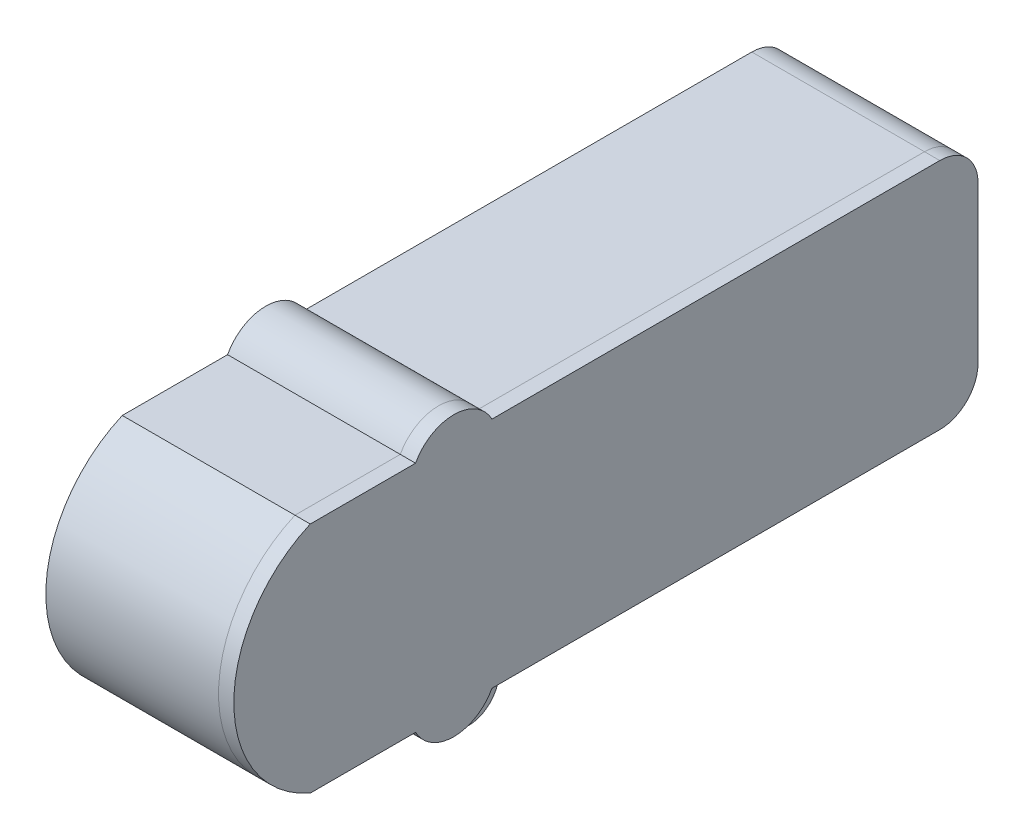
SolidWorks part; units mm, degrees
ref_plane "Front Plane" through (0, 0, 0) normal (0, 0, 1) x (1, 0, 0)
ref_plane "Top Plane" through (0, 0, 0) normal (0, 1, 0) x (1, 0, 0)
ref_plane "Right Plane" through (0, 0, 0) normal (1, 0, 0) x (0, 0, -1)
sketch "Sketch1" plane through (0, 0, 0) normal (1, 0, 0) x (0, 0, -1)
  line L0 (-25.32, -11.25) -> (8.38, -11.25) construction
  line L1 (20.38, -15.25) -> (-67, -15.25)
  line L2 (20.38, -15.25) -> (20.38, 15.25)
  line L3 (20.38, 15.25) -> (-67, 15.25)
  line L4 (-67, -15.25) -> (-67, 15.25) construction
  line L5 (11.38, -8.25) -> (11.38, 8.25) construction
  line L6 (-25.32, -11.25) -> (8.38, -11.25) construction
  line L7 (11.38, -8.25) -> (11.38, 8.25) construction
  line L8 (8.38, 11.25) -> (-25.32, 11.25) construction
  line L9 (8.38, 11.25) -> (-25.32, 11.25) construction
  line L10 (8.38, 15.25) -> (8.38, 11.25) construction
  line L11 (20.38, 8.25) -> (11.38, 8.25) construction
  line L12 (8.38, -11.25) -> (8.38, -15.25) construction
  line L13 (16.38, 2) -> (16.38, -2) construction
  line L14 (16.38, 2) -> (16.38, -2) construction
  line L15 (16.38, 2) -> (20.38, 2) construction
  line L17 (-67, 0) -> (-77, 0) construction
  arc A0 (-67, 15.25) -> (-67, -15.25) centre (-60.3719, 0) ccw
  dimension "D2" = 10
  dimension "D1" = 4
extrude "Boss-Extrude1" add sketch "Sketch1" against normal blind 3
fillet "Fillet1" radius 5 2 edges at (-1.5, -15.25, -20.38) (-1.5, 15.25, -20.38)
sketch "Sketch2" plane through (0, 0, 0) normal (1, 0, 0) x (0, 0, -1)
  line L0 (-66.3438, -12.25) -> (15.38, -12.25)
  line L1 (17.38, -10.25) -> (17.38, 10.25)
  line L2 (15.38, 12.25) -> (-66.3438, 12.25)
  line L3 (-67, -15.25) -> (15.38, -15.25)
  line L4 (20.38, -10.25) -> (20.38, 10.25)
  line L5 (15.38, 15.25) -> (-67, 15.25)
  line L6 (-67, -15.25) -> (15.38, -15.25)
  line L7 (20.38, -10.25) -> (20.38, 10.25)
  line L8 (15.38, 15.25) -> (-67, 15.25)
  arc A0 (15.38, -12.25) -> (17.38, -10.25) centre (15.38, -10.25) ccw
  arc A1 (17.38, 10.25) -> (15.38, 12.25) centre (15.38, 10.25) ccw
  arc A2 (-66.3438, 12.25) -> (-66.3438, -12.25) centre (-60.3719, 0) ccw
  arc A3 (15.38, -15.25) -> (20.38, -10.25) centre (15.38, -10.25) ccw
  arc A4 (20.38, 10.25) -> (15.38, 15.25) centre (15.38, 10.25) ccw
  arc A5 (-67, 15.25) -> (-67, -15.25) centre (-60.3719, 0) ccw
  arc A6 (15.38, -15.25) -> (20.38, -10.25) centre (15.38, -10.25) ccw
  arc A7 (20.38, 10.25) -> (15.38, 15.25) centre (15.38, 10.25) ccw
  arc A8 (-67, 15.25) -> (-67, -15.25) centre (-60.3719, 0) ccw
  dimension "D1" = 0
  dimension "D2" = 3
extrude "Boss-Extrude2" add sketch "Sketch2" along normal offset from surface (19.6 mm away) 1 offset beyond the face yes
sketch "Sketch3" plane through (0, 0, 0) normal (1, 0, 0) x (0, 0, -1)
  line L0 (-34.62, 12.25) -> (-34.62, 11.25)
  line L1 (-66.3438, 12.25) -> (15.38, 12.25) construction
  line L2 (-34.62, 11.25) -> (10.38, 11.25)
  line L3 (11.38, 10.25) -> (11.38, -12.25)
  line L4 (15.38, -12.25) -> (-66.3438, -12.25) construction
  line L5 (11.38, -12.25) -> (15.38, -12.25)
  line L6 (11.38, 8.25) -> (11.38, -8.25) construction
  line L7 (-25.32, 11.25) -> (8.38, 11.25) construction
  line L8 (15.38, 12.25) -> (-66.3438, 12.25) construction
  line L9 (17.38, -10.25) -> (17.38, 10.25) construction
  line L10 (15.38, 12.25) -> (-34.62, 12.25)
  line L11 (17.38, -10.25) -> (17.38, 10.25)
  arc A0 (10.38, 11.25) -> (11.38, 10.25) centre (10.38, 10.25) cw
  arc A1 (17.38, 10.25) -> (15.38, 12.25) centre (15.38, 10.25) ccw construction
  arc A2 (15.38, -12.25) -> (17.38, -10.25) centre (15.38, -10.25) ccw construction
  arc A3 (17.38, 10.25) -> (15.38, 12.25) centre (15.38, 10.25) ccw
  arc A4 (15.38, -12.25) -> (17.38, -10.25) centre (15.38, -10.25) ccw
  dimension "D1" = 1
  dimension "D2" = 45
extrude "Boss-Extrude5" add sketch "Sketch3" along normal up to surface (18.6 mm away)
sketch "Sketch5" plane through (18.6, 0, 0) normal (1, 0, 0) x (0, 0, -1)
  line L4 (17.38, 10.25) -> (17.38, -10.25) construction
  line L5 (10.38, -3.5) -> (17.38, -3.5)
  line L6 (10.38, -3.5) -> (10.38, 3.5)
  line L7 (10.38, 3.5) -> (17.38, 3.5)
  line L12 (17.38, -3.5) -> (17.38, 3.5)
  line L13 (10.38, -3.5) -> (17.38, 3.5) construction
  line L14 (10.38, 3.5) -> (17.38, -3.5) construction
  arc A2 (15.18, 0) -> (12.58, 0) centre (13.88, 0) ccw construction
  arc A3 (15.18, 0) -> (12.58, 0) centre (13.88, 0) ccw construction
extrude "Cut-Extrude1" cut sketch "Sketch5" against normal offset from surface (11.8 mm away) 1 offset beyond the face yes
sketch "Sketch6" plane through (0, 0, 0) normal (1, 0, 0) x (0, 0, -1)
  line L0 (-49.019, 14.805) -> (-47.419, 14.805) construction
  line L1 (-49.019, 14.805) -> (-47.419, 14.805) construction
  line L2 (-49.019, -15.055) -> (-47.419, -15.055) construction
  line L3 (-49.019, -15.055) -> (-47.419, -15.055) construction
  line L4 (-49.019, 14.805) -> (-49.019, -15.055) construction
  line L5 (-47.419, -15.055) -> (-47.419, 14.805) construction
  line L6 (-50.019, 15.805) -> (-46.419, 15.805)
  line L7 (-46.419, -16.055) -> (-46.419, 15.805)
  line L8 (-50.019, -16.055) -> (-46.419, -16.055)
  line L9 (-50.019, 15.805) -> (-50.019, -16.055)
  dimension "D1" = 1
extrude "Cut-Extrude2" cut sketch "Sketch6" along normal through all
sketch "Sketch7" plane through (-3, 0, 0) normal (-1, 0, 0) x (0, 0, 1)
  line L0 (67, 15.25) -> (50.019, 15.25) construction
  line L1 (46.419, 15.25) -> (-15.38, 15.25) construction
  line L6 (48.219, 15.25) -> (48.219, 18.25) construction
  line L7 (50.019, 15.25) -> (46.419, 15.25) construction
  line L8 (53.219, 15.25) -> (43.219, 15.25)
  line L9 (0, 0) -> (12.8243, 0) construction
  line L10 (48.219, -15.25) -> (48.219, -18.25) construction
  line L11 (53.219, -15.25) -> (43.219, -15.25)
  arc A0 (53.219, 15.25) -> (43.219, 15.25) centre (48.219, 12.5833) ccw
  arc A1 (53.219, -15.25) -> (43.219, -15.25) centre (48.219, -12.5833) cw
  dimension "D1" = 10
  dimension "D2" = 3
extrude "Boss-Extrude6" add sketch "Sketch7" against normal up to surface (22.6 mm away) up to face at (19.6, 0, 60.5525)
sketch "Sketch8" plane through (19.6, 0, 0) normal (1, 0, 0) x (0, 0, -1)
  line L5 (-67, -15.25) -> (-53.219, -15.25)
  line L6 (-43.219, -15.25) -> (15.38, -15.25)
  line L7 (20.38, -10.25) -> (20.38, 10.25)
  line L8 (15.38, 15.25) -> (-43.219, 15.25)
  line L9 (-53.219, 15.25) -> (-67, 15.25)
  line L10 (-67, -15.25) -> (-53.219, -15.25)
  line L11 (-43.219, -15.25) -> (15.38, -15.25)
  line L12 (20.38, -10.25) -> (20.38, 10.25)
  line L13 (15.38, 15.25) -> (-43.219, 15.25)
  line L14 (-53.219, 15.25) -> (-67, 15.25)
  arc A5 (-53.219, -15.25) -> (-43.219, -15.25) centre (-48.219, -12.5833) ccw
  arc A6 (15.38, -15.25) -> (20.38, -10.25) centre (15.38, -10.25) ccw
  arc A7 (20.38, 10.25) -> (15.38, 15.25) centre (15.38, 10.25) ccw
  arc A8 (-43.219, 15.25) -> (-53.219, 15.25) centre (-48.219, 12.5833) ccw
  arc A9 (-67, 15.25) -> (-67, -15.25) centre (-60.3719, 0) ccw
  arc A10 (-53.219, -15.25) -> (-43.219, -15.25) centre (-48.219, -12.5833) ccw
  arc A11 (15.38, -15.25) -> (20.38, -10.25) centre (15.38, -10.25) ccw
  arc A12 (20.38, 10.25) -> (15.38, 15.25) centre (15.38, 10.25) ccw
  arc A13 (-43.219, 15.25) -> (-53.219, 15.25) centre (-48.219, 12.5833) ccw
  arc A14 (-67, 15.25) -> (-67, -15.25) centre (-60.3719, 0) ccw
  dimension "D1" = 0
extrude "Boss-Extrude7" add sketch "Sketch8" along normal blind 2 separate body
ref_plane "Plane2" through (9.3, 0, 0) normal (1, 0, 0) x (0, 0, -1)
sketch "Sketch9" plane through (9.3, 0, 0) normal (1, 0, 0) x (0, 0, -1)
  line L0 (-43, -15.25) -> (-43, -21.25)
  line L1 (-43.219, -15.25) -> (15.38, -15.25) construction
  line L2 (-35, -21.25) -> (-35, -15.25)
  line L3 (-35, -15.25) -> (-43, -15.25)
  line L4 (-39, -25.25) -> (-39, -15.25) construction
  line L5 (0, 0) -> (0, -21.25) construction
  line L6 (0, -21.25) -> (-35, -21.25) construction
  arc A0 (-43, -21.25) -> (-35, -21.25) centre (-39, -21.25) ccw
  dimension "D1" = 8
  dimension "D2" = 10
  dimension "D3" = 35
extrude "Boss-Extrude8" add sketch "Sketch9" along normal mid plane 10
